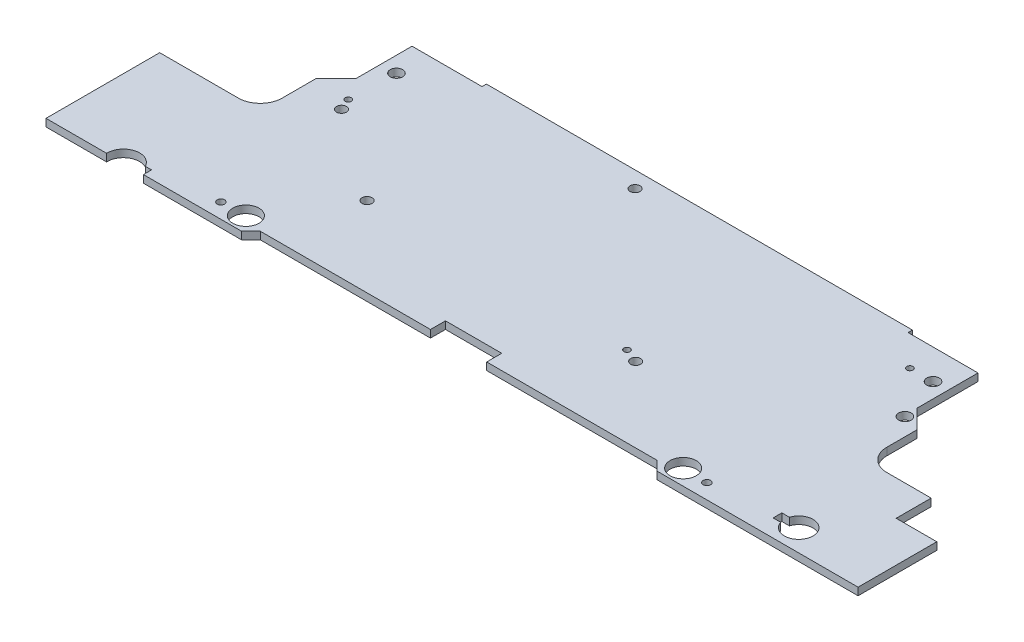
SolidWorks part; units mm, degrees
ref_plane "Plan de face" through (0, 0, 0) normal (0, 0, 1) x (1, 0, 0)
ref_plane "Plan de dessus" through (0, 0, 0) normal (0, 1, 0) x (1, 0, 0)
ref_plane "Plan de droite" through (0, 0, 0) normal (1, 0, 0) x (0, 0, -1)
sketch "Esquisse1" plane through (0, 0, 0) normal (0, 1, 0) x (1, 0, 0)
  line L0 (-64.55, 14.3) -> (-64.55, -3.9)
  line L1 (65.45, 8.7) -> (65.45, -3.9)
  line L2 (65.45, 8.7) -> (58.95, 8.7)
  line L3 (58.95, 8.7) -> (58.95, 14.3)
  line L4 (65.45, -3.9) -> (33.25, -3.9)
  line L5 (33.25, -3.9) -> (31.75, -2.4)
  line L6 (31.75, -2.4) -> (4.5, -2.4)
  line L7 (4.5, 0) -> (-4.5, 0)
  line L8 (4.5, -2.4) -> (4.5, 0)
  line L9 (-4.5, 0) -> (-4.5, -2.4)
  line L10 (-4.5, -2.4) -> (-31.75, -2.4)
  line L11 (-31.75, -2.4) -> (-33.25, -3.9)
  line L12 (-33.25, -3.9) -> (-48.95, -3.9)
  line L13 (-64.55, -3.9) -> (-54.85, -3.9)
  line L14 (-48.95, -3.9) -> (-48.95, -2.6)
  line L15 (-48.95, -2.6) -> (-49.95, -2.6)
  line L16 (-64.55, 14.3) -> (-51.95, 14.3)
  line L17 (58.95, 14.3) -> (51.85, 14.3)
  line L18 (48.35, 17.8) -> (48.35, 22.6)
  line L19 (48.35, 22.6) -> (45.35, 25.6)
  line L20 (45.35, 25.6) -> (45.35, 35.4)
  line L21 (45.35, 35.4) -> (34.15, 35.4)
  line L22 (34.15, 35.4) -> (34.15, 36.1)
  line L23 (34.15, 36.1) -> (-34.05, 36.1)
  line L24 (-34.05, 36.1) -> (-34.05, 35.4)
  line L25 (-34.05, 35.4) -> (-45.25, 35.4)
  line L26 (-45.25, 35.4) -> (-45.25, 26.4)
  line L27 (-45.25, 26.4) -> (-48.45, 23.2)
  line L28 (-48.45, 23.2) -> (-48.45, 17.8)
  line L29 (50.2591, 0.3) -> (49.05, 0.3)
  line L30 (49.05, 0.3) -> (49.05, -1.1)
  line L31 (49.05, -1.1) -> (50.2591, -1.1)
  arc A0 (-54.85, -3.9) -> (-49.95, -2.6) centre (-52.2548, -3.7972) cw
  arc A1 (48.35, 17.8) -> (51.85, 14.3) centre (51.85, 17.8) ccw
  arc A2 (-51.95, 14.3) -> (-48.45, 17.8) centre (-51.95, 17.8) ccw
  circle A3 centre (34.95, -1.4) radius 2.1
  circle A4 centre (52.45, -0.4) radius 2.3
  circle A5 centre (-35.05, -1.4) radius 2.1
  circle A6 centre (-7.65, 33.5) radius 0.8
  circle A7 centre (42.95, 30.6) radius 1
  circle A8 centre (-27.45, 10.4) radius 0.8
  circle A9 centre (16.35, 9.6) radius 0.8
  circle A10 centre (-42.95, 22.9) radius 0.5
  circle A11 centre (-42.75, 30.4) radius 1
  circle A12 centre (45.55, 23.5) radius 1
  circle A13 centre (14.05, 10.5) radius 0.5
  circle A14 centre (-42.15, 21) radius 0.8
  circle A15 centre (-38.95, -1.5) radius 0.6
  circle A16 centre (39.25, 30.6) radius 0.5
  circle A17 centre (38.85, -1.5) radius 0.6
  point P17 (-52.2548, -1.2)
  point P19 (34.95, -3.5)
  point P24 (0, 0)
  point P37 (52.45, -2.7)
  point P38 (54.75, -0.4)
  point P41 (48.35, 14.3)
  point P44 (-48.45, 14.3)
  point P47 (37.05, -1.4)
  point P50 (-35.05, -3.5)
  point P51 (-37.15, -1.4)
  point P56 (46.55, 23.5)
  point P57 (45.55, 24.5)
  point P60 (42.95, 31.6)
  point P61 (39.75, 30.6)
  point P64 (39.25, 31.1)
  point P67 (38.85, -2.1)
  point P70 (39.45, -1.5)
  point P71 (16.35, 8.8)
  point P74 (17.15, 9.6)
  point P75 (-27.45, 9.6)
  point P78 (-28.25, 10.4)
  point P79 (-42.15, 20.2)
  point P82 (-42.95, 21)
  point P85 (-43.75, 30.4)
  point P88 (-42.75, 31.4)
  point P91 (-42.15, 21.8)
  point P92 (-38.95, -2.1)
  point P93 (-38.35, -1.5)
  point P94 (43.95, 30.6)
  point P95 (-42.95, 23.4)
  point P96 (-8.45, 33.5)
  point P97 (-7.65, 34.3)
  point P98 (14.05, 10)
  point P99 (15.55, 9.6)
  point P100 (14.55, 10.5)
  point P101 (38.25, -1.5)
  point P102 (45.55, 22.5)
  point P107 (0, 0)
  point P108 (48.6977, -1.3639)
  point P109 (49.05, -0.4)
  point P110 (48.4846, 0.5858)
  dimension "D29" = 3.5
  dimension "D30" = 4.2
  dimension "D33" = 4.6
  dimension "D36" = 4.2
  dimension "D39" = 1.6
  dimension "D40" = 2
  dimension "D41" = 1.6
  dimension "D42" = 1
  dimension "D43" = 1.6
  dimension "D44" = 1.6
  dimension "D45" = 1
  dimension "D46" = 1
  dimension "D47" = 2
  dimension "D48" = 2
  dimension "D57" = 1.2
  dimension "D67" = 1.2
  dimension "D1" = 130
  dimension "D2" = 12.6
  dimension "D3" = 18.2
  dimension "D4" = 6.5
  dimension "D5" = 5.6
  dimension "D6" = 32.2
  dimension "D7" = 1.5
  dimension "D8" = 1.5
  dimension "D9" = 1.3
  dimension "D10" = 9
  dimension "D11" = 2.4
  dimension "D12" = 5.9
  dimension "D13" = 1.5
  dimension "D14" = 1.5
  dimension "D15" = 15.7
  dimension "D16" = 9.7
  dimension "D17" = 2.7
  dimension "D18" = 1
  dimension "D19" = 16.1
  dimension "D20" = 10.6
  dimension "D21" = 8.3
  dimension "D22" = 3
  dimension "D23" = 39.3
  dimension "D24" = 40
  dimension "D25" = 11.2
  dimension "D26" = 11.2
  dimension "D27" = 90.6
  dimension "D28" = 9
  dimension "D31" = 0.4
  dimension "D32" = 1.2
  dimension "D34" = 10.7
  dimension "D35" = 28.4
  dimension "D37" = 0.4
  dimension "D38" = 27.4
  dimension "D49" = 4
  dimension "D50" = 1.5
  dimension "D51" = 13.6
  dimension "D52" = 5.5
  dimension "D53" = 36.3
  dimension "D54" = 12
  dimension "D55" = 1.8
  dimension "D56" = 1.2
  dimension "D58" = 12
  dimension "D59" = 1.8
  dimension "D60" = 36.8
  dimension "D61" = 11.2
  dimension "D62" = 41.8
  dimension "D63" = 12.4
  dimension "D64" = 1
  dimension "D65" = 1.8
  dimension "D66" = 1.2
  dimension "D68" = 3.8
  dimension "D69" = 1.4
  dimension "D70" = 5.6
  dimension "D71" = 4.3
  dimension "D72" = 1.8
  dimension "D73" = 26.4
  dimension "D74" = 1.4
  dimension "D75" = 5.7
extrude "Boss.-Extru.1" add sketch "Esquisse1" along normal blind 1.2 contours L28 A2 L16 L0 L13 A0 L15 L14 L12 L11 L10 L9 L7 L8 L6 L5 L4 L1 L2 L3 L17 A1 L18 L19 L20 L21 L22 L23 L24 L25 L26 L27
extrude "Enlèv. mat.-Extru.1" cut sketch "Esquisse1<4>" along normal blind 1.2 contours A5 | A14 | A8 | A11 | A6 | A13 | A9 | A3 | A17 | A4 | A4 L29 L30 L31 | A12 | A7 | A16 | A15 | A10 region at (49.6185, 0, 0.4) region at (52.45, 0, 0.4) region at (34.95, 0, 1.4) region at (-35.05, 0, 1.4) region at (-7.65, 0, -33.5) region at (42.95, 0, -30.6) region at (-27.45, 0, -10.4) region at (16.35, 0, -9.6) region at (-42.75, 0, -30.4) region at (45.55, 0, -23.5) region at (14.05, 0, -10.5) region at (-42.15, 0, -21) region at (39.25, 0, -30.6) region at (38.85, 0, 1.5)
sketch "Esquisse1<4>" plane through (0, 0, 0) normal (0, 1, 0) x (1, 0, 0) same geometry as "Esquisse1"
